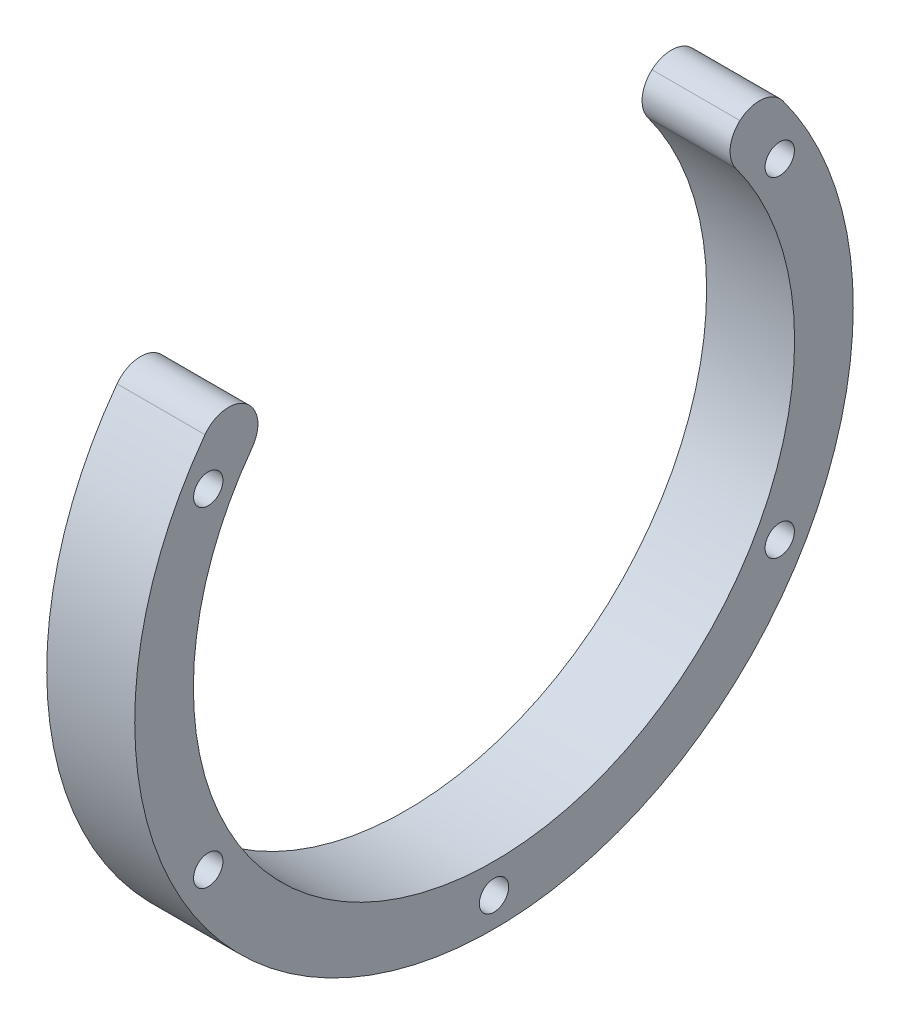
SolidWorks part; units mm, degrees
material "1060 Alloy"
ref_plane "Front Plane" through (0, 0, 0) normal (0, 0, 1) x (1, 0, 0)
ref_plane "Top Plane" through (0, 0, 0) normal (0, 1, 0) x (1, 0, 0)
ref_plane "Right Plane" through (0, 0, 0) normal (1, 0, 0) x (0, 0, -1)
sketch "Sketch1" plane through (0, 0, 0) normal (1, 0, 0) x (0, 0, -1)
  circle A0 centre (0, 0) radius 49
  circle A1 centre (0, 0) radius 41
extrude "Boss-Extrude1" add sketch "Sketch1" along normal blind 12
hole_wizard "Ø4.0mm Dowel Hole1" positions "Sketch2" profile "Sketch3" hole size "Ø4.0" standard "ISO"
sketch "Sketch2" plane through (12, 0, 0) normal (1, 0, 0) x (0, 0, -1)
  line L0 (0, 44.2539) -> (0, -44.2539) construction
  line L1 (55, 0) -> (-55, 0) construction
  point P0 (0, 45)
  dimension "D1" = 45
sketch "Sketch3" plane through (12, 45, 0) normal (0, 1, 0) x (0, 0, -1)
  line L0 (0, 0) -> (0, 51.2017)
  line L1 (0, 51.2017) -> (2, 50)
  line L2 (2, 50) -> (2, 0)
  line L5 (2, 0) -> (0, 0)
  line L10 (0, 51.2017) -> (-2, 50) construction
  line L11 (0, -6.35) -> (0, 107.95) construction
  dimension "Hole Dia." = 4
  dimension "Hole Depth" = 50
  dimension "Drill Angle" = 118
pattern_circular "CirPattern1" count 6 over 360 about axis through (12, 0, 0) along (1, 0, 0) of "Ø4.0mm Dowel Hole1"
sketch "Sketch4" plane through (12, 0, 0) normal (1, 0, 0) x (0, 0, -1)
  line L0 (-36.6708, 32.5) -> (0, 0)
  line L1 (0, 0) -> (36.6708, 32.5)
  arc A0 (-36.6708, 32.5) -> (36.6708, 32.5) centre (0, 0) cw
  circle A1 centre (0, 0) radius 49 construction
  circle A2 centre (-38.9711, 22.5) radius 2 construction
  circle A3 centre (38.9711, 22.5) radius 2 construction
  dimension "D1" = 10
  dimension "D2" = 10
extrude "Cut-Extrude1" cut sketch "Sketch4" against normal blind 12
fillet "Fillet1" radius 4 4 edges at (6, 32.5, -36.6708) (6, 27.1939, -30.6838) (6, 27.1939, 30.6838) (6, 32.5, 36.6708)
